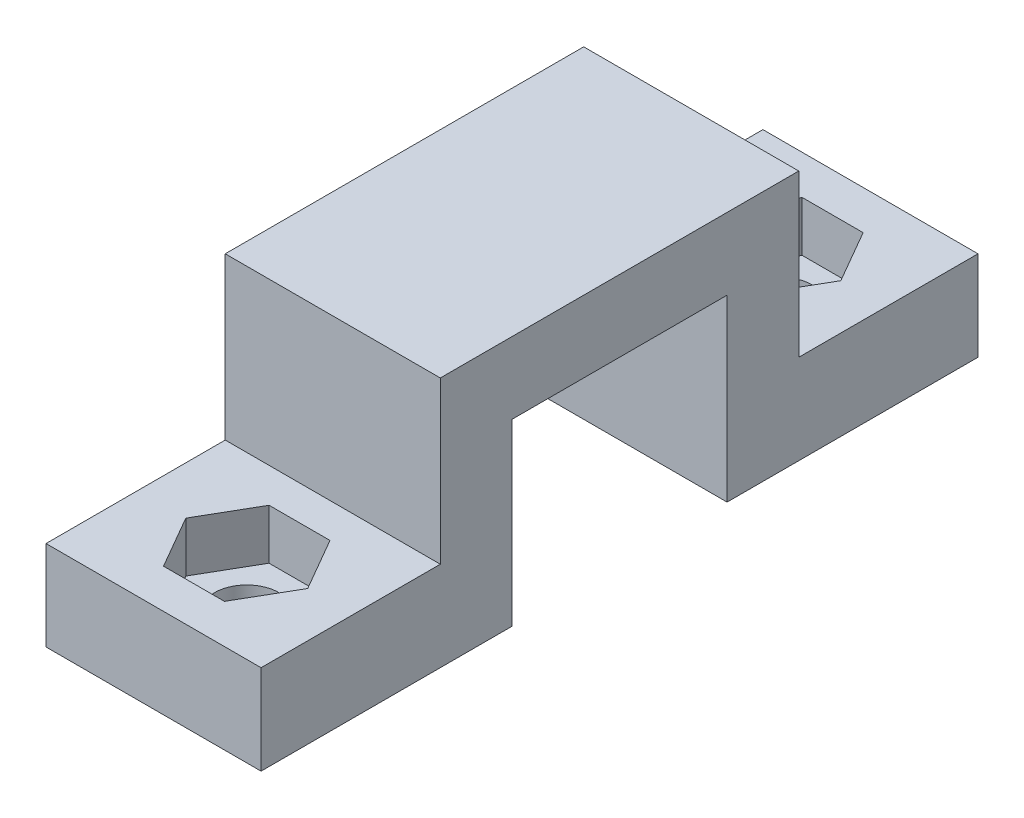
SolidWorks part; units mm, degrees
ref_plane "Plano frontal" through (0, 0, 0) normal (0, 0, 1) x (1, 0, 0)
ref_plane "Plano superior" through (0, 0, 0) normal (0, 1, 0) x (1, 0, 0)
ref_plane "Plano direito" through (0, 0, 0) normal (1, 0, 0) x (0, 0, -1)
sketch "Esboço1" plane through (0, 0, 0) normal (0, 1, 0) x (1, 0, 0)
  line L1 (6, -10) -> (-6, -10)
  line L2 (6, -10) -> (6, 10)
  line L3 (6, 10) -> (-6, 10)
  line L4 (-6, -10) -> (-6, 10)
  line L5 (6, -10) -> (-6, 10) construction
  line L6 (6, 10) -> (-6, -10) construction
  point P0 (0, 0)
  dimension "D1" = 20
  dimension "D2" = 12
extrude "Ressalto-extrusão1" add sketch "Esboço1" along normal blind 14
sketch "Esboço5" plane through (6, 0, 0) normal (1, 0, 0) x (0, 0, -1)
  line L0 (-6, 14) -> (-6, -49986) construction
  line L2 (6, 14) -> (6, -49986) construction
  line L4 (-10, 10) -> (49990, 10) construction
  line L6 (-10, 14) -> (10, 14) construction
  line L7 (-10, 14) -> (-10, 0) construction
  line L8 (10, 14) -> (10, 0) construction
  line L9 (-10, 0) -> (10, 0) construction
  line L11 (-6, 10) -> (6, 10)
  line L12 (-6, 10) -> (-6, 0)
  line L13 (-6, 0) -> (6, 0)
  line L14 (6, 10) -> (6, 0)
  dimension "D1" = 4
  dimension "D2" = 4
  dimension "D3" = 4
extrude "Corte-extrusão1" cut sketch "Esboço5" against normal blind 12
sketch "Esboço6" plane through (0, 0, 10) normal (0, 0, 1) x (1, 0, 0)
  line L0 (-6, 5) -> (49994, 5) construction
  line L1 (-6, 14) -> (-6, 0) construction
  line L2 (-6, 0) -> (6, 0) construction
  line L3 (6, 0) -> (-6, 0)
  line L4 (6, 0) -> (6, 5)
  line L5 (6, 5) -> (-6, 5)
  line L6 (-6, 0) -> (-6, 5)
  dimension "D1" = 5
extrude "Ressalto-extrusão2" add sketch "Esboço6" along normal blind 10 and the other way blind 30
sketch "Esboço7" plane through (6, 0, 0) normal (1, 0, 0) x (0, 0, -1)
  line L0 (-20, 0) -> (20, 0) construction
  line L1 (-6, 5) -> (6, 5)
  line L2 (-6, 5) -> (-6, 0)
  line L3 (-6, 0) -> (6, 0)
  line L4 (6, 5) -> (6, 0)
extrude "Corte-extrusão2" cut sketch "Esboço7" against normal blind 12
sketch "Esboço8" plane through (0, 5, 0) normal (0, 1, 0) x (1, 0, 0)
  line L0 (6, 17.9) -> (-49994, 17.9) construction
  line L1 (-6, 20) -> (-6, 10) construction
  line L2 (-1.6264, 17.817) -> (1.7736, 17.817)
  line L3 (6, 12.1) -> (-49994, 12.1) construction
  line L4 (6, 20) -> (6, 10) construction
  line L5 (2.9, 20) -> (2.9, -49980) construction
  line L6 (6, 20) -> (-6, 20) construction
  line L7 (-2.9, 20) -> (-2.9, -49980) construction
  line L8 (6, 10) -> (-6, 10) construction
  line L9 (1.7736, 17.817) -> (3.4736, 14.8725)
  line L10 (3.4736, 14.8725) -> (1.7736, 11.928)
  line L11 (1.7736, 11.928) -> (-1.6264, 11.928)
  line L12 (-1.6264, 11.928) -> (-3.3264, 14.8725)
  line L13 (-3.3264, 14.8725) -> (-1.6264, 17.817)
  line L14 (-1.6264, 17.817) -> (1.7736, 11.928)
  line L15 (0, 0) -> (50000, 0) construction
  line L16 (-1.6264, -17.817) -> (1.7736, -11.928)
  line L17 (-3.3264, -14.8725) -> (-1.6264, -17.817)
  line L18 (-1.6264, -11.928) -> (-3.3264, -14.8725)
  line L19 (1.7736, -11.928) -> (-1.6264, -11.928)
  line L20 (3.4736, -14.8725) -> (1.7736, -11.928)
  line L21 (1.7736, -17.817) -> (3.4736, -14.8725)
  line L22 (-1.6264, -17.817) -> (1.7736, -17.817)
  circle A0 centre (0.0736, 14.8725) radius 1.8
  circle A1 centre (0.0736, -14.8725) radius 1.8
  point P12 (-6, 15)
  dimension "D1" = 3.1
  dimension "D2" = 3.1
  dimension "D3" = 2.1
  dimension "D4" = 2.1
  dimension "D5" = 120
  dimension "D6" = 3.4
  dimension "D7" = 120
  dimension "D8" = 120
  dimension "D9" = 120
  dimension "D10" = 120
  dimension "D11" = 120
  dimension "D12" = 3.4
  dimension "D13" = 3.4
  dimension "D14" = 3.4
  dimension "D15" = 3.4
  dimension "D16" = 3.4
extrude "Corte-extrusão3" cut sketch "Esboço8" against normal blind 5 contours A0
extrude "Corte-extrusão4" cut sketch "Esboço8<3>" against normal blind 5 contours A1 L16 | A1 L16 region at (-0.588, 5, 14.4906) region at (0.7352, 5, 15.2545)
sketch "Esboço8<3>" plane through (0, 5, 0) normal (0, 1, 0) x (1, 0, 0) same geometry as "Esboço8"
extrude "Corte-extrusão5" cut sketch "Esboço8<4>" against normal blind 2.8 contours A0 L14 L10 L9 L2 | A0 L14 L13 L12 L11 | L16 A1 L19 L18 L17 | L16 A1 L22 L21 L20 region at (-1.2939, 5, -17.0852) region at (0.0736, 5, -17.7391) region at (-2.4089, 5, 16.3058) region at (-1.1589, 5, 17.1631)
sketch "Esboço8<4>" plane through (0, 5, 0) normal (0, 1, 0) x (1, 0, 0) same geometry as "Esboço8"
